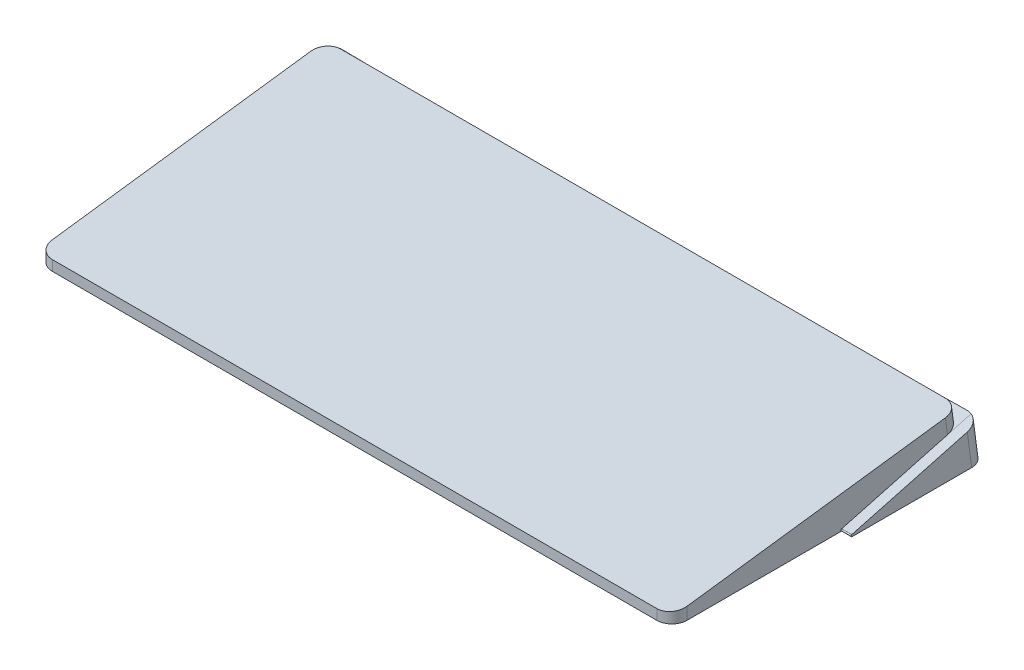
SolidWorks part; units mm, degrees
ref_plane "Front Plane" through (0, 0, 0) normal (0, 0, 1) x (1, 0, 0)
ref_plane "Top Plane" through (0, 0, 0) normal (0, 1, 0) x (1, 0, 0)
ref_plane "Right Plane" through (0, 0, 0) normal (1, 0, 0) x (0, 0, -1)
sketch "Sketch1" plane through (0, 0, 0) normal (0, 1, 0) x (1, 0, 0)
  line L1 (-157.5, 75.665) -> (157.5, 75.665)
  line L2 (-157.5, 75.665) -> (-157.5, -75.665)
  line L3 (-157.5, -75.665) -> (157.5, -75.665)
  line L4 (157.5, 75.665) -> (157.5, -75.665)
  line L5 (-157.5, 75.665) -> (157.5, -75.665) construction
  line L6 (-157.5, -75.665) -> (157.5, 75.665) construction
  point P0 (0, 0)
  dimension "D1" = 315
  dimension "D2" = 151.33
extrude "Boss-Extrude1" add sketch "Sketch1" along normal blind 25
sketch "Sketch2" plane through (0, 0, 0) normal (1, 0, 0) x (0, 0, -1)
  line L0 (-75.665, 5.077) -> (75.665, 25)
  line L1 (-75.665, 25) -> (-75.665, 0) construction
  line L2 (75.665, 25) -> (-75.665, 25)
  line L3 (-75.665, 25) -> (75.665, 25) construction
  line L4 (-75.665, 25) -> (-75.665, 5.077)
  line L5 (75.665, 0) -> (72.4298, 24.5741)
  line L6 (75.665, 25) -> (75.665, 0) construction
  line L7 (75.665, 25) -> (75.665, 0)
  dimension "D1" = 7.5
extrude "Cut-Extrude1" cut sketch "Sketch2" against normal through all both and the other way through all contours L2 L4 L0 | L7 L0 L5 region at (0, 18.359, 25.2217) region at (0, 16.5247, -74.5866)
sketch "Sketch5" plane through (0, 0, 0) normal (1, 0, 0) x (0, 0, -1)
  line L0 (5, 0) -> (73.2441, 18.3884)
  line L1 (75.665, 0) -> (-75.665, 0) construction
  line L2 (75.665, 0) -> (72.4298, 24.5741) construction
  line L3 (73.2441, 18.3884) -> (75.665, 0)
  line L4 (75.665, 0) -> (5, 0)
  line L5 (70.8818, 17.7519) -> (75.665, 0) construction
  dimension "D1" = 5
  dimension "D2" = 18.385
extrude "Boss-Extrude2" add sketch "Sketch5" against normal mid plane 325
sketch "Sketch6" plane through (0, 9.7918, -74.3759) normal (0, 0.1305, -0.9914) x (-1, 0, 0)
  line L1 (-162.5, -9.8763) -> (162.5, -9.8763) construction
  line L2 (-42.7831, -1.1964) -> (42.7831, -1.1964) construction
  line L3 (-157.5, 8.6708) -> (-162.5, 8.6708) construction
  line L4 (0, -9.8763) -> (0, 14.9099) construction
  line L5 (157.5, 14.9099) -> (-157.5, 14.9099) construction
  line L7 (-157.5, 14.9099) -> (157.5, 14.9099)
  line L8 (-157.5, 14.9099) -> (-157.5, 28.7758)
  line L9 (-157.5, 28.7758) -> (157.5, 28.7758)
  line L10 (157.5, 14.9099) -> (157.5, 28.7758)
  line L14 (-157.5, 14.9099) -> (-157.5, 8.6708)
  line L15 (-157.5, 8.6708) -> (-162.5, 8.6708)
  line L16 (-162.5, 8.6708) -> (-162.5, -9.8763)
  line L17 (-162.5, -9.8763) -> (162.5, -9.8763)
  line L18 (162.5, -9.8763) -> (162.5, 8.6708)
  line L19 (162.5, 8.6708) -> (157.5, 8.6708)
  line L20 (157.5, 8.6708) -> (157.5, 14.9099)
  line L21 (157.5, 14.9099) -> (-157.5, 14.9099)
  line L22 (-157.5, 14.9099) -> (-157.5, 8.6708)
  line L23 (-157.5, 8.6708) -> (-162.5, 8.6708)
  line L24 (-162.5, 8.6708) -> (-162.5, -9.8763)
  line L25 (-162.5, -9.8763) -> (162.5, -9.8763)
  line L26 (162.5, -9.8763) -> (162.5, 8.6708)
  line L27 (162.5, 8.6708) -> (157.5, 8.6708)
  line L28 (157.5, 8.6708) -> (157.5, 14.9099)
  line L29 (157.5, 14.9099) -> (-157.5, 14.9099)
  arc A0 (-42.7831, -1.1964) -> (42.7831, -1.1964) centre (0, 245.6643) ccw
  arc A1 (-42.7831, -1.1964) -> (-157.5, 8.6708) centre (-157.5, -663.1192) ccw
  arc A2 (42.7831, -1.1964) -> (157.5, 8.6708) centre (157.5, -663.1192) cw
  point P5 (0, -4.8763)
  line M14 (-157.5, 14.9099) -> (-157.5, 8.6708)
  line M20 (157.5, 8.6708) -> (157.5, 14.9099)
  line M21 (157.5, 14.9099) -> (-157.5, 14.9099)
  dimension "D1" = 5
  dimension "D2" = 0
extrude "Cut-Extrude4" cut sketch "Sketch6" along direction (0, -0.2602, 0.9656) on the side against the normal blind 5 contours A0 A2 A1 M20 M21 M14 | L8 L7 L10 L9 region at (0, 17.6938, -73.3356)
fillet "Fillet2" radius 0.5 2 edges at (160, 0, -5) (-160, 0, -5)
fillet "Fillet1" radius 7.5 6 edges at (-157.5, 2.5385, 75.665) (157.5, 2.5385, 75.665) (-162.5, 9.1942, -74.4546) (162.5, 9.1942, -74.4546)
sketch "Sketch4" plane through (0, 0, 0) normal (0, 1, 0) x (1, 0, 0)
  line L1 (-160.1297, 68.0505) -> (160.1297, 68.0505)
  line L2 (-160.1297, 68.0505) -> (-160.1297, -68.0505)
  line L3 (-160.1297, -68.0505) -> (160.1297, -68.0505)
  line L4 (160.1297, 68.0505) -> (160.1297, -68.0505)
  line L5 (-160.1297, 68.0505) -> (160.1297, -68.0505) construction
  line L6 (-160.1297, -68.0505) -> (160.1297, 68.0505) construction
  point P0 (0, 0)
extrude "Cut-Extrude3" [suppressed] cut sketch "Sketch4" against normal blind 10 from surface starting at face at (0, 14.5038, 4.0619)
